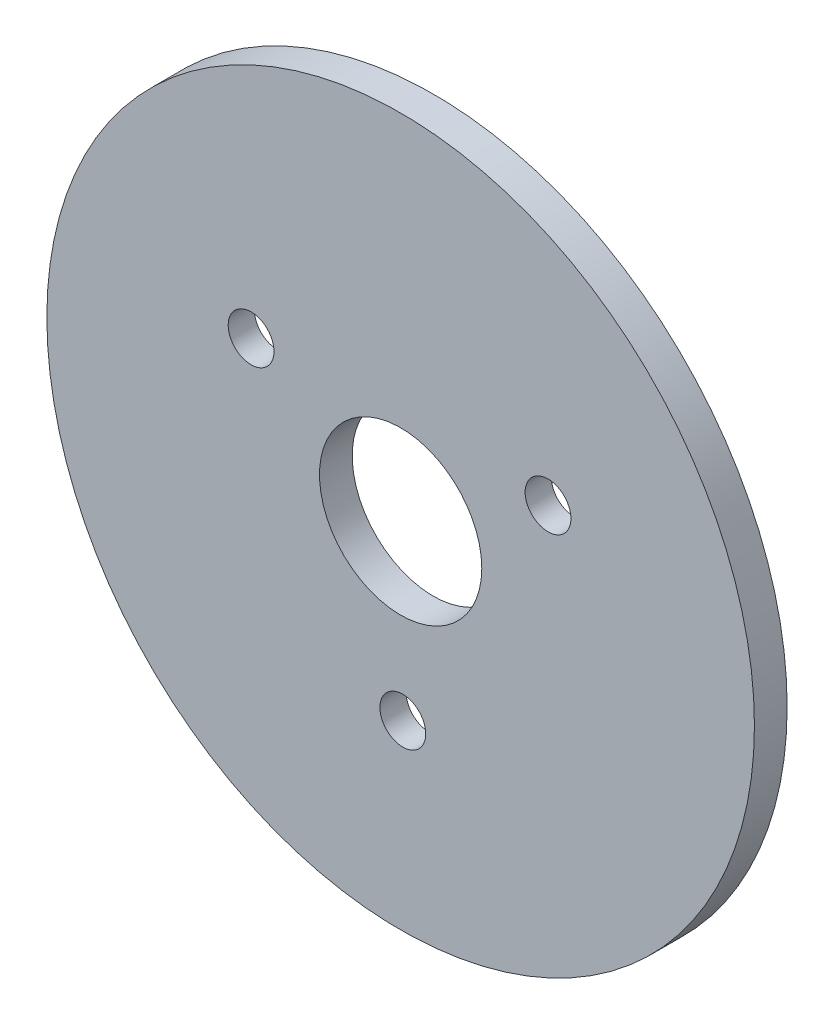
SolidWorks part; units mm, degrees
ref_plane "Front Plane" through (0, 0, 0) normal (0, 0, 1) x (1, 0, 0)
ref_plane "Top Plane" through (0, 0, 0) normal (0, 1, 0) x (1, 0, 0)
ref_plane "Right Plane" through (0, 0, 0) normal (1, 0, 0) x (0, 0, -1)
sketch "Sketch1" plane through (0, 0, 0) normal (0, 1, 0) x (1, 0, 0)
  line L0 (0, 36.1296) -> (0, -19.4741) construction
sketch "Sketch7" plane through (0, 0, 0) normal (0, 0, 1) x (1, 0, 0)
  line L0 (0, 0) -> (0, 20.9536) construction
  line L1 (-2.325, 21.9086) -> (-2.9401, 23.5986) construction
  line L2 (-2.325, 21.9086) -> (-1.6298, 19.9986) construction
  line L3 (-1.6298, 19.9986) -> (1.6298, 19.9986) construction
  line L4 (1.6298, 19.9986) -> (2.325, 21.9086) construction
  line L5 (2.325, 21.9086) -> (-2.325, 21.9086) construction
  line L6 (0, 19.9986) -> (0, 21.9086) construction
  line L7 (2.325, 21.9086) -> (2.9401, 23.5986) construction
  line L8 (-2.9401, 23.5986) -> (2.9401, 23.5986) construction
  line L9 (0, 0) -> (8.5226, 19.1421) construction
  line L10 (8.5226, 19.1421) -> (8.9611, 20.1269) construction
  line L11 (0, 21.9086) -> (0, 22.0316) construction
  line L12 (0, 22.0316) -> (0, 23.7811) construction
  line L13 (0, 22.9064) -> (9.3169, 20.926) construction
  line L14 (8.9611, 20.1269) -> (9.6726, 21.7251) construction
  circle A1 centre (0, 0) radius 20.9536 construction
  circle A2 centre (-1.2727, 20.5086) radius 0.51 construction
  circle A3 centre (1.2727, 20.5086) radius 0.51 construction
  circle A4 centre (0, 0) radius 22.0316
  circle A5 centre (0, 0) radius 23.7811 construction
  dimension "D3" = 40
  dimension "D6" = 1.02
  dimension "D1" = 3.6
  dimension "D2" = 24
  dimension "D7" = 9.525
  dimension "D4" = 1.91
  dimension "D5" = 4.65
extrude "Boss-Extrude1" add sketch "Sketch7" along normal blind 7.25 and the other way blind 7.25 contours A4 region at (0, 0, 0)
sketch "Sketch14" plane through (0, 0, 0) normal (1, 0, 0) x (0, 0, -1)
  line L0 (-18, 0) -> (-18, 10)
  line L1 (-18, 0) -> (0, 0)
  line L2 (0, 0) -> (0, 19)
  line L3 (0, 19) -> (-7.25, 19)
  line L4 (-7.25, 19) -> (-18, 10)
  line L5 (-7.25, 22.0316) -> (-7.25, -22.0316) construction
  line L6 (-18, 6.7395) -> (-3.3555, 19) construction
  arc A0 (-7.25, 19) -> (-18, 10) centre (-18.1316, 21.0773) cw
  dimension "D1" = 10
  dimension "D2" = 19
  dimension "D3" = 18
  dimension "D4" = 2.5
revolve "Revolve1" add sketch "Sketch14" angle 360 about L0 region at (0, 7.5733, 7.5341) region at (0, 9.2725, 16.1663) region at (0, 17.2765, 6.6188)
sketch "Sketch9" plane through (0, 0, 0) normal (0, 0, 1) x (1, 0, 0)
  line L0 (2, 0) -> (-2, 0) construction
  line L1 (-2, 0) -> (-2, 7.5) construction
  line L2 (-2, 7.5) -> (2, 7.5) construction
  line L3 (2, 7.5) -> (2, 0) construction
  circle A0 centre (0, 0) radius 6 construction
  dimension "D1" = 12
  dimension "D2" = 4
  dimension "D3" = 7.5
sketch "Sketch10" plane through (0, 0, 0) normal (0, 0, 1) x (1, 0, 0)
  line L0 (2, 0) -> (-2, 0) construction
  line L1 (-2.2, 7.7) -> (2.2, 7.7)
  line L2 (-2.2, 7.7) -> (-2.2, 0)
  line L3 (-2.2, 0) -> (2.2, 0)
  line L4 (2.2, 7.7) -> (2.2, 0)
  line L5 (-2, 7.5) -> (2, 7.5) construction
  line L6 (2, 7.5) -> (2, 0) construction
  circle A0 centre (0, 0) radius 6.2
  circle A1 centre (0, 0) radius 6 construction
  dimension "D1" = 0.2
  dimension "D2" = 0.2
  dimension "D3" = 0.2
extrude "Cut-Extrude3" cut sketch "Sketch10" against normal through all both and the other way through all contours A0 L4 L1 L2 | L2 A0 L4 L3 | L4 A0 L2 L3 region at (0, 6.8793, 0) region at (0, 3.0348, 0) region at (0, -0.8613, 0)
sketch "Sketch11" plane through (0, 0, 0) normal (0, 1, 0) x (1, 0, 0)
  line L0 (22.0316, 7.25) -> (-22.0316, 7.25) construction
  line L1 (11, 7.25) -> (17.5, 7.25)
  line L2 (11, 7.25) -> (11, 4.75)
  line L3 (11, 4.75) -> (17.5, 4.75)
  line L4 (17.5, 7.25) -> (17.5, 4.75)
  line L5 (-22.0316, -7.25) -> (22.0316, -7.25) construction
  line L6 (11, -7.25) -> (17.5, -7.25)
  line L7 (11, -7.25) -> (11, -4.75)
  line L8 (11, -4.75) -> (17.5, -4.75)
  line L9 (17.5, -7.25) -> (17.5, -4.75)
  line L11 (11, 4.75) -> (11, -4.75) construction
  line L12 (17.5, -4.75) -> (17.5, 4.75) construction
  line L13 (6.2, 7.25) -> (-6.2, 7.25) construction
  line L14 (0, 7.25) -> (22.5, 7.25)
  line L15 (0, 7.25) -> (0, -7.25)
  line L16 (0, -7.25) -> (22.5, -7.25)
  line L17 (22.5, 7.25) -> (22.5, -7.25)
  line L18 (-6.2, -7.25) -> (6.2, -7.25) construction
  line L19 (6, 7.25) -> (6, -7.25) construction
  dimension "D1" = 22.5
  dimension "D2" = 6
  dimension "D3" = 5
  dimension "D4" = 5
  dimension "D5" = 2.5
revolve "Cut-Revolve1" [suppressed] cut sketch "Sketch11" angle 360 about L0
sketch "Sketch15" plane through (0, 0, -7.25) normal (0, 0, -1) x (-1, 0, 0)
  circle A0 centre (0, 0) radius 8.0081
  circle A1 centre (0, 0) radius 2.25
  dimension "D1" = 4.5
extrude "Boss-Extrude2" add sketch "Sketch15" against normal blind 5.5
sketch "Sketch16" plane through (0, 0, -7.25) normal (0, 0, -1) x (-1, 0, 0)
  circle A0 centre (0, 0) radius 5
  dimension "D1" = 10
extrude "Cut-Extrude4" cut sketch "Sketch16" against normal blind 3
sketch "Sketch17" plane through (0, 0, -7.25) normal (0, 0, -1) x (-1, 0, 0)
  circle A0 centre (0, 0) radius 22.0316
  circle A1 centre (0, 0) radius 22.0316 construction
  circle A2 centre (0, 0) radius 5
  circle A3 centre (0, 0) radius 5 construction
extrude "Boss-Extrude3" add sketch "Sketch17" along normal blind 7.5
sketch "Sketch8" plane through (0, 0, 0) normal (0, 0, 1) x (1, 0, 0)
  line L6 (-1.6298, 19.9986) -> (-2.3698, 22.0316)
  line L7 (-2.3698, 22.0316) -> (2.3698, 22.0316)
  line L8 (2.3698, 22.0316) -> (1.6298, 19.9986)
  line L9 (1.6298, 19.9986) -> (-1.6298, 19.9986)
  line L10 (-2.325, 21.9086) -> (-1.6298, 19.9986) construction
  line L11 (1.6298, 19.9986) -> (2.325, 21.9086) construction
  line L12 (6.6453, 18.9326) -> (6.7962, 21.0908)
  line L13 (6.7962, 21.0908) -> (11.126, 19.163)
  line L14 (11.126, 19.163) -> (9.6231, 17.6067)
  line L15 (9.6231, 17.6067) -> (6.6453, 18.9326)
  line L16 (13.7713, 14.5929) -> (14.787, 16.5031)
  line L17 (14.787, 16.5031) -> (17.9584, 12.981)
  line L18 (17.9584, 12.981) -> (15.9524, 12.1705)
  line L19 (15.9524, 12.1705) -> (13.7713, 14.5929)
  line L20 (18.5162, 7.73) -> (20.221, 9.0619)
  line L21 (20.221, 9.0619) -> (21.6856, 4.5544)
  line L22 (21.6856, 4.5544) -> (19.5235, 4.6299)
  line L23 (19.5235, 4.6299) -> (18.5162, 7.73)
  line L24 (20.0594, -0.4695) -> (22.1587, 0.0539)
  line L25 (22.1587, 0.0539) -> (21.6632, -4.6597)
  line L26 (21.6632, -4.6597) -> (19.7187, -3.7113)
  line L27 (19.7187, -3.7113) -> (20.0594, -0.4695)
  line L28 (18.1342, -8.5879) -> (20.2649, -8.9635)
  line L29 (20.2649, -8.9635) -> (17.8951, -13.0681)
  line L30 (17.8951, -13.0681) -> (16.5044, -11.4108)
  line L31 (16.5044, -11.4108) -> (18.1342, -8.5879)
  line L32 (13.0734, -15.2212) -> (14.8671, -16.4311)
  line L33 (14.8671, -16.4311) -> (11.0327, -19.2169)
  line L34 (11.0327, -19.2169) -> (10.4363, -17.1372)
  line L35 (10.4363, -17.1372) -> (13.0734, -15.2212)
  line L36 (5.7521, -19.2227) -> (6.8986, -21.0575)
  line L37 (6.8986, -21.0575) -> (2.2626, -22.0429)
  line L38 (2.2626, -22.0429) -> (2.5637, -19.9005)
  line L39 (2.5637, -19.9005) -> (5.7521, -19.2227)
  line L40 (-2.5637, -19.9005) -> (-2.2626, -22.0429)
  line L41 (-2.2626, -22.0429) -> (-6.8986, -21.0575)
  line L42 (-6.8986, -21.0575) -> (-5.7521, -19.2227)
  line L43 (-5.7521, -19.2227) -> (-2.5637, -19.9005)
  line L44 (-10.4363, -17.1372) -> (-11.0327, -19.2169)
  line L45 (-11.0327, -19.2169) -> (-14.8671, -16.4311)
  line L46 (-14.8671, -16.4311) -> (-13.0734, -15.2212)
  line L47 (-13.0734, -15.2212) -> (-10.4363, -17.1372)
  line L48 (-16.5044, -11.4108) -> (-17.8951, -13.0681)
  line L49 (-17.8951, -13.0681) -> (-20.2649, -8.9635)
  line L50 (-20.2649, -8.9635) -> (-18.1342, -8.5879)
  line L51 (-18.1342, -8.5879) -> (-16.5044, -11.4108)
  line L52 (-19.7187, -3.7113) -> (-21.6632, -4.6597)
  line L53 (-21.6632, -4.6597) -> (-22.1587, 0.0539)
  line L54 (-22.1587, 0.0539) -> (-20.0594, -0.4695)
  line L55 (-20.0594, -0.4695) -> (-19.7187, -3.7113)
  line L56 (-19.5235, 4.6299) -> (-21.6856, 4.5544)
  line L57 (-21.6856, 4.5544) -> (-20.221, 9.0619)
  line L58 (-20.221, 9.0619) -> (-18.5162, 7.73)
  line L59 (-18.5162, 7.73) -> (-19.5235, 4.6299)
  line L60 (-15.9524, 12.1705) -> (-17.9584, 12.981)
  line L61 (-17.9584, 12.981) -> (-14.787, 16.5031)
  line L62 (-14.787, 16.5031) -> (-13.7713, 14.5929)
  line L63 (-13.7713, 14.5929) -> (-15.9524, 12.1705)
  line L64 (-9.6231, 17.6067) -> (-11.126, 19.163)
  line L65 (-11.126, 19.163) -> (-6.7962, 21.0908)
  line L66 (-6.7962, 21.0908) -> (-6.6453, 18.9326)
  line L67 (-6.6453, 18.9326) -> (-9.6231, 17.6067)
  circle A0 centre (0, 0) radius 22.0316 construction
  point P119 (0, 0)
  dimension "D1" = 15
extrude "Cut-Extrude2" cut sketch "Sketch8" against normal through all both and the other way through all
fillet "Fillet2" radius 0.51 60 edges at (-6.787, 20.9602, -3.75) (-11.035, 19.0689, -3.75) (-14.7256, 16.3875, -3.75) (-17.837, 12.9319, -3.75) (-20.1179, 8.9813, -3.75) (-21.5548, 4.5589, -3.75) (-22.0316, 0.0222, -3.75) (-21.5456, -4.6023, -3.75) (-20.1359, -8.9408, -3.75) (-17.8109, -12.9678, -3.75) (-14.7585, -16.3578, -3.75) (-10.9966, -19.0911, -3.75) (-6.8293, -20.9465, -3.75) (-2.2809, -21.9133, -3.75) (2.2809, -21.9133, -3.75) (6.8293, -20.9465, -3.75) (10.9966, -19.0911, -3.75) (14.7585, -16.3578, -3.75) (17.8109, -12.9678, -3.75) (20.1359, -8.9408, -3.75) (21.5456, -4.6023, -3.75) (22.0316, 0.0222, -3.75) (21.5548, 4.5589, -3.75) (20.1179, 8.9813, -3.75) (17.837, 12.9319, -3.75) (14.7256, 16.3875, -3.75) (11.035, 19.0689, -3.75) (6.787, 20.9602, -3.75) (2.325, 21.9086, -3.75) (-6.6453, 18.9326, -3.75) (-9.6231, 17.6067, -3.75) (-13.7713, 14.5929, -3.75) (-15.9524, 12.1705, -3.75) (-18.5162, 7.73, -3.75) (-19.5235, 4.6299, -3.75) (-20.0594, -0.4695, -3.75) (-19.7187, -3.7113, -3.75) (-18.1342, -8.5879, -3.75) (-16.5044, -11.4108, -3.75) (-13.0734, -15.2212, -3.75) (-10.4363, -17.1372, -3.75) (-5.7521, -19.2227, -3.75) (-2.5637, -19.9005, -3.75) (2.5637, -19.9005, -3.75) (5.7521, -19.2227, -3.75) (10.4363, -17.1372, -3.75) (13.0734, -15.2212, -3.75) (16.5044, -11.4108, -3.75) (18.1342, -8.5879, -3.75) (19.7187, -3.7113, -3.75) (20.0594, -0.4695, -3.75) (19.5235, 4.6299, -3.75) (18.5162, 7.73, -3.75) (15.9524, 12.1705, -3.75) (13.7713, 14.5929, -3.75) (9.6231, 17.6067, -3.75) (6.6453, 18.9326, -3.75) (1.6298, 19.9986, -3.75) (-1.6298, 19.9986, -3.75) (-2.325, 21.9086, -3.75)
sketch "Sketch18" plane through (0, 0, -14.75) normal (0, 0, -1) x (-1, 0, 0)
  circle A0 centre (0, 0) radius 5
  circle A1 centre (0, 0) radius 27.0316
  circle A2 centre (0, 0) radius 22.0316
  circle A3 centre (0, 0) radius 5 construction
  arc A4 (-2.7297, 21.8619) -> (-6.3983, 21.0821) centre (0, 0) ccw construction
  dimension "D1" = 5
extrude "Boss-Extrude4" add sketch "Sketch18" along normal blind 2.5 contours A1 A2 | A2 A0 region at (26.2671, 0, -14.75) region at (21.4085, 0, -14.75)
sketch "Sketch19" plane through (0, 0, 7.25) normal (0, 0, 1) x (1, 0, 0)
  circle A0 centre (0, 0) radius 19
  circle A1 centre (0, 0) radius 27.0316
  circle A2 centre (0, 0) radius 27.0316 construction
  circle A3 centre (0, 0) radius 19 construction
extrude "Boss-Extrude5" add sketch "Sketch19" against normal blind 2.5
fillet "Fillet3" [suppressed] radius 0.5
sketch "Sketch20" plane through (0, 0, 18) normal (0, 0, 1) x (1, 0, 0)
  line L0 (-2.2, 5.7966) -> (-2.2, 7.7)
  line L1 (-2.2, 7.7) -> (2.2, 7.7)
  line L2 (-2.2, 7.7) -> (2.2, 7.7) construction
  line L3 (2.2, 7.7) -> (2.2, 5.7966)
  circle A0 centre (0, 0) radius 6.2
  arc A1 (-2.2, 5.7966) -> (2.2, 5.7966) centre (0, 0) ccw construction
  arc M2 (2.2, 5.7966) -> (-2.2, 5.7966) centre (0, 0) cw
  line M3 (-2.2, 5.7966) -> (-2.2, 7.7)
  line M4 (-2.2, 7.7) -> (2.2, 7.7)
  line M5 (2.2, 7.7) -> (2.2, 5.7966)
extrude "Cut-Extrude5" cut sketch "Sketch20" against normal through all contours A0 M5 M4 M3 | A0 M2 region at (0, 6.8793, 18) region at (0, 0, 18)
ref_plane "Plane1" through (0, 0, -5.25) normal (0, 0, 1) x (1, 0, 0)
sketch "Sketch21" plane through (0, 0, -5.25) normal (0, 0, 1) x (1, 0, 0)
  circle A0 centre (0, 0) radius 8.0081
  circle A1 centre (0, 0) radius 2.25
  circle A2 centre (0, 0) radius 6.2
  arc A3 (-2.2, 5.7966) -> (2.2, 5.7966) centre (0, 0) ccw construction
  dimension "D1" = 4.5
extrude "Boss-Extrude6" add sketch "Sketch21" against normal blind 2.5 contours A2 A1 | A0 A2 region at (-7.7816, 0, -5.25) region at (-6.0246, 0, -5.25)
extrude "Boss-Extrude7" add sketch "Sketch21<4>" against normal up to surface (12 mm away) contours A0 A2 region at (-7.7816, 0, -5.25) up to face at (0, 3.7491, -17.25)
sketch "Sketch21<4>" plane through (0, 0, -5.25) normal (0, 0, 1) x (1, 0, 0) same geometry as "Sketch21"
sketch "Sketch22" plane through (0, 0, 0) normal (0, 1, 0) x (1, 0, 0)
  line L0 (-27.0316, 17.25) -> (-27.0316, 14.75) construction
  line L1 (-27.0316, 17.25) -> (27.0316, 17.25)
  line L2 (-27.0316, 17.25) -> (-27.0316, 14.75)
  line L3 (-27.0316, 14.75) -> (27.0316, 14.75)
  line L4 (27.0316, 17.25) -> (27.0316, 14.75)
  line L5 (-27.0316, 17.25) -> (27.0316, 14.75) construction
  line L6 (-27.0316, 14.75) -> (27.0316, 17.25) construction
  line L7 (-10, -18) -> (10, -18) construction
  line L8 (-27.0316, 14.75) -> (27.0316, 14.75)
  line L9 (-27.0316, 14.75) -> (-27.0316, -18)
  line L10 (-27.0316, -18) -> (27.0316, -18)
  line L11 (27.0316, 14.75) -> (27.0316, -18)
  point P0 (0, 16)
extrude "Cut-Extrude6" cut sketch "Sketch22" against normal through all both and the other way through all contours L11 L3 L9 L10 region at (0, 0, 1.625)
sketch "Sketch24" plane through (0, 0, -17.25) normal (0, 0, -1) x (-1, 0, 0)
  circle A1 centre (11.4264, 6.4055) radius 1.75
  circle A2 centre (-11.2605, 6.6928) radius 1.75
  circle A3 centre (-0.1659, -13.0983) radius 1.75
  circle A4 centre (-11.2605, 6.6928) radius 5
  circle A5 centre (11.4264, 6.4055) radius 5
  circle A6 centre (-0.1659, -13.0983) radius 5
  point P12 (0, 0)
  dimension "D1" = 3.5
  dimension "D2" = 10
extrude "Cut-Extrude7" cut sketch "Sketch24" against normal through all contours A1 | A3 | A2 region at (-11.4264, 6.4055, -17.25) region at (11.2605, 6.6928, -17.25) region at (0.1659, -13.0983, -17.25)
extrude "Cut-Extrude8" cut sketch "Sketch24<3>" against normal blind 0.5
sketch "Sketch24<3>" plane through (0, 0, -17.25) normal (0, 0, -1) x (-1, 0, 0) same geometry as "Sketch24"
fillet "Fillet4" radius 0.5 3 edges at (-4.8341, -13.0983, -17.25) (-16.4264, 6.4055, -17.25) (6.2605, 6.6928, -17.25)
